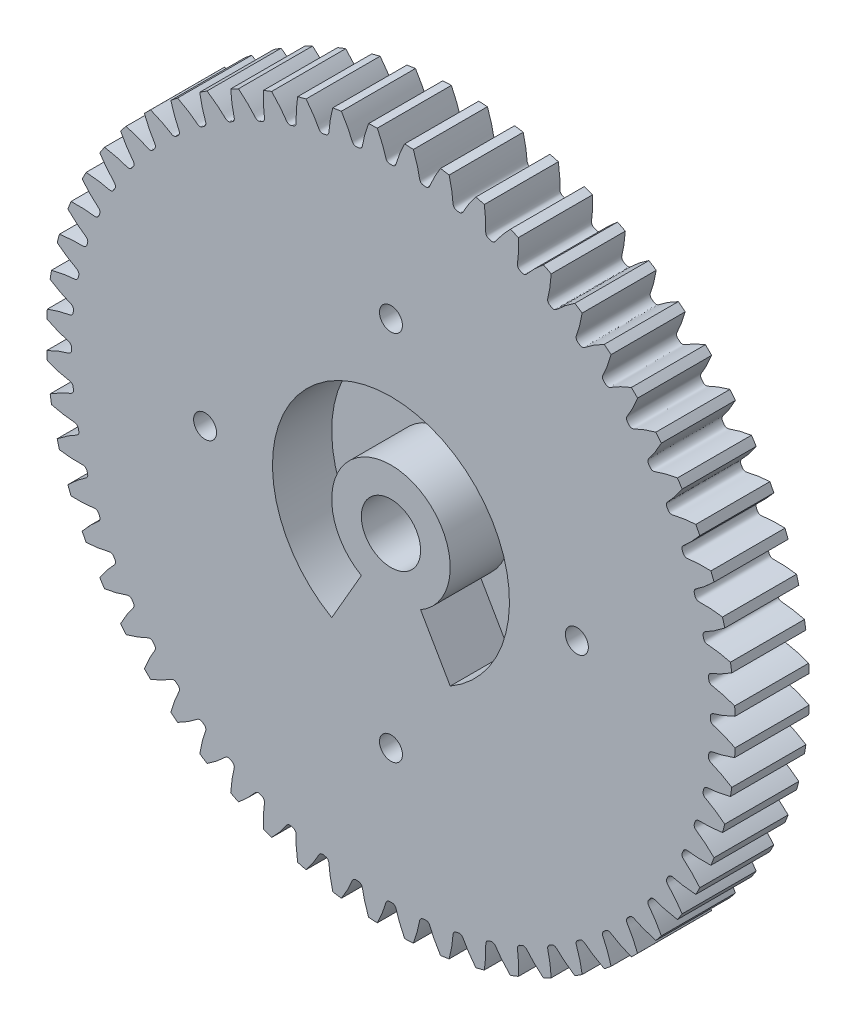
SolidWorks part; units mm, degrees
ref_plane "Front Plane" through (0, 0, 0) normal (0, 0, 1) x (1, 0, 0)
ref_plane "Top Plane" through (0, 0, 0) normal (0, 1, 0) x (1, 0, 0)
ref_plane "Right Plane" through (0, 0, 0) normal (1, 0, 0) x (0, 0, -1)
ref_axis "Axis1" through (0, 0, 5.5) along (0, 0, -1)
sketch "SketchRevolveSpurAssembly01Gear" plane through (0, 0, 0) normal (1, 0, 0) x (0, 0, -1)
  line L0 (0, 0) -> (1, 0) construction
  line L1 (-5, 0) -> (-5, 46.5)
  line L2 (-5, 46.5) -> (5, 46.5)
  line L3 (5, 46.5) -> (5, 0)
  line L4 (5, 0) -> (-5, 0)
  dimension "Side1" = 5
  dimension "OutsideRadius" = 46.5
  dimension "Side2" = 5
revolve "SpurAssembly01Gear" add sketch "SketchRevolveSpurAssembly01Gear" angle 360 about L0
sketch "SketchToothSpurAssembly01Gear" plane through (0, 0, 0) normal (0, 0, 1) x (1, 0, 0)
  arc A0 (46.5369, 1.8824) -> (46.5369, -1.8824) centre (0, 0) cw
  spline S0 degree 3 poles (46.5369, -1.8824) (46.4106, -1.8178) (46.2223, -1.724) (45.9725, -1.6049) (45.7913, -1.5209) (45.614, -1.4411) (45.4406, -1.3655) (45.2713, -1.2938) (45.1061, -1.2261) (44.945, -1.1621) (44.7882, -1.1018) (44.6356, -1.0452) (44.4874, -0.992) (44.3436, -0.9422) (44.2043, -0.8957) (44.0695, -0.8523) (43.9392, -0.8123) (43.7554, -0.7565) (43.5912, -0.7185) (43.4569, -0.6604) (43.397, -0.6284) (43.3333, -0.5856) (43.2647, -0.5249) (43.195, -0.4361) (43.14, -0.3154) (43.1191, -0.1635) (43.1282, 0) (43.1191, 0.1635) (43.14, 0.3154) (43.195, 0.4361) (43.2647, 0.5249) (43.3333, 0.5856) (43.397, 0.6284) (43.4569, 0.6604) (43.5912, 0.7185) (43.7554, 0.7565) (43.9392, 0.8123) (44.0695, 0.8523) (44.2043, 0.8957) (44.3436, 0.9422) (44.4874, 0.992) (44.6356, 1.0452) (44.7882, 1.1018) (44.945, 1.1621) (45.1061, 1.2261) (45.2713, 1.2938) (45.4406, 1.3655) (45.614, 1.4411) (45.7913, 1.5209) (45.9725, 1.6049) (46.2223, 1.724) (46.4106, 1.8178) (46.5369, 1.8824) knots 0 0 0 0 0.051766 0.076686 0.100963 0.124598 0.147592 0.169943 0.191651 0.212718 0.233143 0.252925 0.272065 0.290563 0.308419 0.325633 0.342204 0.358133 0.395729 0.403327 0.411415 0.420483 0.431261 0.444675 0.461387 0.478965 0.5 0.521035 0.538613 0.555325 0.568739 0.579517 0.588585 0.596673 0.604271 0.641867 0.657796 0.674367 0.691581 0.709437 0.727935 0.747075 0.766857 0.787282 0.808349 0.830057 0.852408 0.875402 0.899037 0.923314 0.948234 1 1 1 1
extrude "ToothExtrudeCutSpurAssembly01Gear" cut sketch "SketchToothSpurAssembly01Gear" against normal blind 5 and the other way blind 5
pattern_circular "PatternSpurAssembly01Gear" count 60 over 360 about axis through (0, 0, 5.5) along (0, 0, -1) of "ToothExtrudeCutSpurAssembly01Gear"
sketch "AuxiliarySketchSpurAssembly01Gear" plane through (0, 0, 0) normal (0, 0, 1) x (1, 0, 0)
  circle A0 centre (0, 0) radius 45 construction
  circle A1 centre (0, 0) radius 42.2862 construction
  circle A2 centre (0, 0) radius 43.6372 construction
  circle A3 centre (0, 0) radius 46.5 construction
  circle A4 centre (0, 0) radius 43.125 construction
  dimension "PitchDiameter" = 90
  dimension "BaseDiameter" = 84.5723
  dimension "FormDiameter" = 87.2745
  dimension "MajorDiameter" = 93
  dimension "MinorDiameter" = 86.25
sketch "Sketch3" plane through (0, 0, 5) normal (0, 0, 1) x (1, 0, 0)
  circle A0 centre (0, 0) radius 4
sketch "Sketch4" plane through (0, 0, 5) normal (0, 0, 1) x (1, 0, 0)
  line L0 (0, 0) -> (-9.5, -16.4545) construction
  line L1 (0, 0) -> (9.5, -16.4545) construction
  line L2 (-4, -6.9282) -> (-8, -13.8564)
  line L3 (4, -6.9282) -> (8, -13.8564)
  arc A1 (8, -13.8564) -> (-8, -13.8564) centre (0, 0) ccw
  arc A2 (4, -6.9282) -> (-4, -6.9282) centre (0, 0) ccw
sketch "Sketch5" plane through (0, 0, -5) normal (0, 0, -1) x (-1, 0, 0)
  circle A0 centre (0, 0) radius 4
extrude "Cut-Extrude2" cut sketch "Sketch5" against normal blind 18
sketch "Sketch6" plane through (0, 0, -5) normal (0, 0, -1) x (-1, 0, 0)
  circle A0 centre (25.1, 0) radius 1.55
extrude "Cut-Extrude3" cut sketch "Sketch6" against normal blind 10
pattern_circular "CirPattern2" count 4 over 360 about axis through (0, 0, 5.5) along (0, 0, -1) of "Cut-Extrude3"
extrude "Cut-Extrude4" cut sketch "Sketch4" against normal blind 8
sketch "Sketch7" plane through (0, 0, -5) normal (0, 0, -1) x (-1, 0, 0)
  circle A0 centre (-25.1, 0) radius 3.5
  circle A1 centre (0, 25.1) radius 3.5
  circle A2 centre (25.1, 0) radius 3.5
  circle A3 centre (0, -25.1) radius 3.5
  point P12 (0, 0)
  dimension "D1" = 4
extrude "Cut-Extrude5" cut sketch "Sketch7" against normal blind 3
